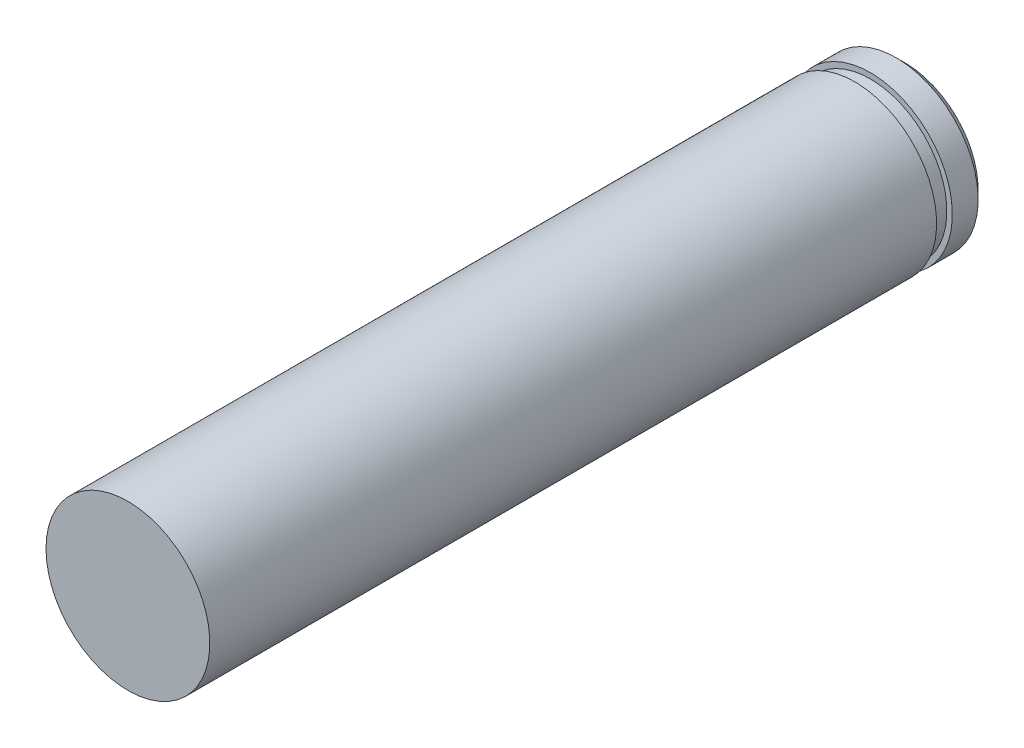
SolidWorks part; units mm, degrees
material "AISI 1020"
ref_plane "Front" through (0, 0, 0) normal (0, 0, 1) x (1, 0, 0)
ref_plane "Top" through (0, 0, 0) normal (0, 1, 0) x (1, 0, 0)
ref_plane "Right" through (0, 0, 0) normal (1, 0, 0) x (0, 0, -1)
ref_axis "side-side" through (80.9, 0, 0) along (-1, 0, 0)
ref_axis "up-down" through (0, 50, 0) along (0, -1, 0)
ref_axis "front-back" through (0, 0, -80.9) along (0, 0, 1)
sketch "Sketch1" plane through (0, 0, 0) normal (1, 0, 0) x (0, 0, -1)
  line L0 (0, 0) -> (-13.9748, 0) construction
  line L1 (0, 0) -> (22.5812, 0)
  line L2 (0, 0) -> (0, 2.3813)
  line L3 (0, 2.3813) -> (21.124, 2.3813)
  line L4 (22.5812, 0) -> (22.5812, 2.3813)
  line L6 (21.124, 2.3813) -> (21.124, 2.2225)
  line L7 (21.124, 2.2225) -> (21.5812, 2.2225)
  line L8 (21.5812, 2.3813) -> (21.5812, 2.2225)
  line L9 (21.5812, 2.3813) -> (22.5812, 2.3813)
  dimension "D1" = 0.4572
  dimension "D2" = 4.445
  dimension "D3" = 4.7625
  dimension "D4" = 1
  dimension "D5" = 21.124
revolve "Revolve1" add sketch "Sketch1" angle 360 about L0
chamfer "Chamfer1" distance 0.25 angle 45 1 edges at (-2.3813, 0, -22.5812)
